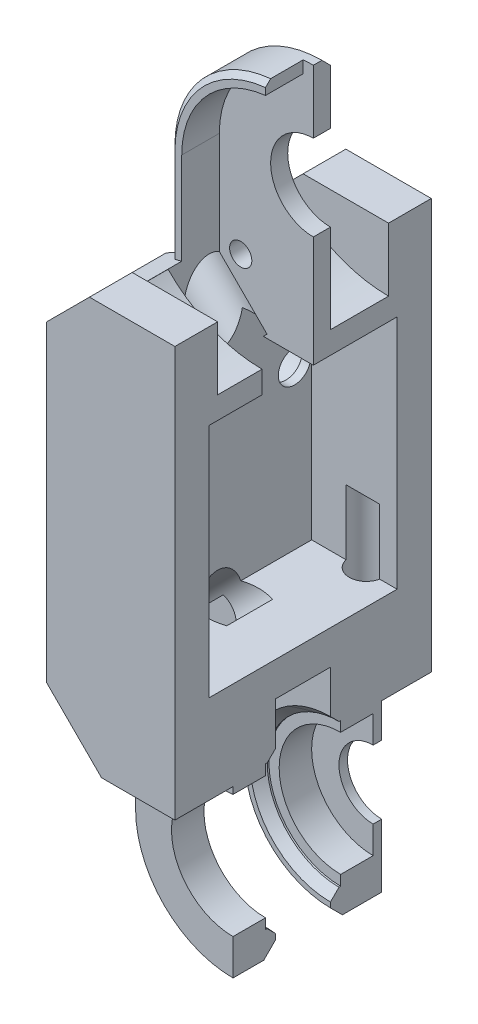
SolidWorks part; units mm, degrees
ref_plane "前视基准面" through (0, 0, 0) normal (0, 0, 1) x (1, 0, 0)
ref_plane "上视基准面" through (0, 0, 0) normal (0, 1, 0) x (1, 0, 0)
ref_plane "右视基准面" through (0, 0, 0) normal (1, 0, 0) x (0, 0, -1)
other "Configuration Table"
sketch "草图1" plane through (0, 0, 0) normal (0, 0, 1) x (1, 0, 0)
  line L0 (6.2, 9) -> (6.2, 0) construction
  line L1 (0, 0) -> (12.4, 0)
  line L2 (0, 0) -> (0, 9)
  line L4 (12.4, 0) -> (12.4, 9)
  arc A0 (0, 9) -> (12.4, 9) centre (6.2, 9) cw
  circle A1 centre (6.2, 9) radius 2.5
  circle A2 centre (1.95, 3.5) radius 0.65
  circle A3 centre (10.45, 3.5) radius 0.65
  dimension "D1" = 12.4
  dimension "D3" = 5
  dimension "D4" = 1.3
  dimension "D2" = 9
  dimension "D5" = 8.5
  dimension "D6" = 5.5
extrude "凸台-拉伸1" add sketch "草图1" along normal blind 1
sketch "草图2" plane through (0, 0, 1) normal (0, 0, 1) x (1, 0, 0)
  line L0 (0.7, 9) -> (0.7, 0)
  line L1 (0, 0) -> (12.4, 0) construction
  line L2 (11.7, 9) -> (11.7, 0)
  line L6 (0, 9) -> (0, 0)
  line L7 (0, 0) -> (12.4, 0)
  line L8 (12.4, 0) -> (12.4, 9)
  line L9 (0, 9) -> (0, 0)
  line L10 (0, 0) -> (12.4, 0)
  line L11 (12.4, 0) -> (12.4, 9)
  circle A0 centre (6.2, 9) radius 5.5
  arc A2 (12.4, 9) -> (0, 9) centre (6.2, 9) ccw
  arc A3 (12.4, 9) -> (0, 9) centre (6.2, 9) ccw
  line M5 (0, 9) -> (0, 0)
  line M6 (0, 0) -> (12.4, 0)
  line M7 (12.4, 0) -> (12.4, 9)
  arc M8 (12.4, 9) -> (0, 9) centre (6.2, 9) ccw
  dimension "D1" = 11
  dimension "D2" = 0
extrude "凸台-拉伸2" add sketch "草图2" along normal blind 2.2 contours A0 L2 L0 M6 M7 M8 M5
sketch "草图3" plane through (0, 0, 3.2) normal (0, 0, 1) x (1, 0, 0)
  line L0 (6.2, 0) -> (6.2, 14.5) construction
  line L1 (5.6, 15.6668) -> (6.8, 15.6668)
  line L2 (5.6, 15.6668) -> (5.6, 13.6792)
  line L3 (5.6, 13.6792) -> (6.8, 13.6792)
  line L4 (6.8, 15.6668) -> (6.8, 13.6792)
  line L5 (0.7, 0) -> (11.7, 0) construction
  arc A0 (11.7, 9) -> (0.7, 9) centre (6.2, 9) ccw construction
  dimension "D1" = 1.2
extrude "切除-拉伸1" cut sketch "草图3" against normal up to surface (2.2 mm away) up to face at (6.2, 5.875, 1)
sketch "草图16" plane through (0, 0, 3.2) normal (0, 0, 1) x (1, 0, 0)
  line L0 (6.2, 0) -> (6.2, 15.1709) construction
  line L2 (13.7, 0) -> (-1.3, 0)
  line L3 (13.7, 0) -> (13.7, 5)
  line L4 (13.7, 5) -> (-1.3, 5)
  line L5 (6.8, 14.4672) -> (6.8, 15.1709)
  line L6 (5.6, 15.1709) -> (5.6, 14.4672)
  line L7 (0.7, 9) -> (0.7, 0)
  line L8 (0.7, 0) -> (11.7, 0)
  line L9 (11.7, 0) -> (11.7, 9)
  line L10 (6.8, 14.4672) -> (6.8, 15.1709)
  line L11 (5.6, 15.1709) -> (5.6, 14.4672)
  line L12 (0.7, 9) -> (0.7, 0)
  line L13 (0.7, 0) -> (11.7, 0)
  line L14 (11.7, 0) -> (11.7, 9)
  line L15 (-1.3, 0) -> (-1.3, 5)
  line L16 (-1.3, 0) -> (13.7, 0)
  line L17 (-1.3, 0) -> (-1.3, -19)
  line L18 (-1.3, -19) -> (13.7, -19)
  line L19 (13.7, 0) -> (13.7, -19)
  arc A3 (11.7, 9) -> (6.8, 14.4672) centre (6.2, 9) ccw
  arc A4 (6.8, 15.1709) -> (5.6, 15.1709) centre (6.2, 9) ccw
  arc A5 (5.6, 14.4672) -> (0.7, 9) centre (6.2, 9) ccw
  arc A6 (11.7, 9) -> (6.8, 14.4672) centre (6.2, 9) ccw
  arc A7 (6.8, 15.1709) -> (5.6, 15.1709) centre (6.2, 9) ccw
  arc A8 (5.6, 14.4672) -> (0.7, 9) centre (6.2, 9) ccw
  line M18 (11.7, 0) -> (12.4, 0)
  line M19 (12.4, 0) -> (12.4, 9)
  dimension "D2" = 5
  dimension "D3" = 15
  dimension "D4" = 19
  dimension "D1" = 0
extrude "凸台-拉伸11" add sketch "草图16" along normal blind 5.9 and the other way blind 9.1 contours L19 L2 L16 L17 L18 M18 | L15 L2 L12 L4 | L3 L4 L2 M19
sketch "草图17" plane through (0, 0, -5.9) normal (0, 0, -1) x (-1, 0, 0)
  line L8 (-13.7, 5) -> (-13.7, -19)
  line L9 (-13.7, -19) -> (1.3, -19)
  line L10 (1.3, -19) -> (1.3, 5)
  line L11 (1.3, 5) -> (-0.7, 5)
  line L12 (-0.7, 5) -> (-0.7, 0)
  line L13 (-0.7, 0) -> (-12.4, 0)
  line L14 (-12.4, 0) -> (-12.4, 5)
  line L15 (-12.4, 5) -> (-13.7, 5)
  line L16 (-13.7, 5) -> (-13.7, -19)
  line L17 (-13.7, -19) -> (1.3, -19)
  line L18 (1.3, -19) -> (1.3, 5)
  line L19 (1.3, 5) -> (-0.7, 5)
  line L20 (-0.7, 5) -> (-0.7, 0)
  line L21 (-0.7, 0) -> (-12.4, 0)
  line L22 (-12.4, 0) -> (-12.4, 5)
  line L23 (-12.4, 5) -> (-13.7, 5)
  arc A1 (-11.9, 9) -> (-0.5, 9) centre (-6.2, 9) ccw
  circle A2 centre (-6.2, 9) radius 7.7
  line M14 (-0.7, 0) -> (-12.4, 0)
  line M15 (-12.4, 0) -> (-12.4, 5)
  dimension "D1" = 2
  dimension "D2" = 0
extrude "凸台-拉伸12" add sketch "草图17" against normal up to surface (5.9 mm away) contours A2 L20 M15 M14 up to face at (5.5143, 5.6, 0)
sketch "草图18" plane through (0, 0, 9.1) normal (0, 0, 1) x (1, 0, 0)
  line L8 (13.7, -19) -> (13.7, 5)
  line L9 (13.7, 5) -> (12.4, 5)
  line L10 (12.4, 5) -> (12.4, 0)
  line L11 (12.4, 0) -> (0.7, 0)
  line L12 (0.7, 0) -> (0.7, 5)
  line L13 (0.7, 5) -> (-1.3, 5)
  line L14 (-1.3, 5) -> (-1.3, -19)
  line L15 (-1.3, -19) -> (13.7, -19)
  line L16 (13.7, -19) -> (13.7, 5)
  line L17 (13.7, 5) -> (12.4, 5)
  line L18 (12.4, 5) -> (12.4, 0)
  line L19 (12.4, 0) -> (0.7, 0)
  line L20 (0.7, 0) -> (0.7, 5)
  line L21 (0.7, 5) -> (-1.3, 5)
  line L22 (-1.3, 5) -> (-1.3, -19)
  line L23 (-1.3, -19) -> (13.7, -19)
  arc A1 (0.5, 9) -> (11.9, 9) centre (6.2, 9) ccw
  circle A2 centre (6.2, 9) radius 7.7
  line M12 (12.4, 0) -> (0.7, 0)
  line M13 (0.7, 0) -> (0.7, 5)
  dimension "D1" = 2
  dimension "D2" = 0
extrude "凸台-拉伸13" add sketch "草图18" against normal blind 5.1 contours A2 L18 M13 M12
sketch "草图19" plane through (-1.3, 0, 0) normal (-1, 0, 0) x (0, 0, 1)
  line L0 (-5.9, 4.4338) -> (-5.9, 1.3) construction
  line L1 (-5.9, 5) -> (-3.4, 5)
  line L2 (-5.9, 5) -> (-5.9, 1.3)
  line L3 (-5.9, 1.3) -> (-3.4, 1.3)
  line L4 (-3.4, 5) -> (-3.4, 1.3)
  line L5 (9.1, 5) -> (6.6, 5)
  line L6 (9.1, 5) -> (9.1, 1.3)
  line L7 (9.1, 1.3) -> (6.6, 1.3)
  line L8 (6.6, 5) -> (6.6, 1.3)
  line L9 (-5.9, 4.4338) -> (-5.9, 1.3)
  line M5 (9.1, -19) -> (9.1, 5)
  line M6 (9.1, 5) -> (-5.9, 5)
  line M7 (-5.9, 5) -> (-5.9, -19)
  dimension "D1" = 2.5
  dimension "D2" = 2.5
extrude "凸台-拉伸14" add sketch "草图19" against normal up to surface (15 mm away) contours L8 L7 M6 M5 | L4 L2 L3 M6 M7 up to face at (13.7, -7, 1.6)
ref_plane "基准面2" through (0, 0, 1.6) normal (0, 0, -1) x (-1, 0, 0)
sketch "草图21" plane through (0, 0, 1.6) normal (0, 0, -1) x (-1, 0, 0)
  line L0 (1.3, -19) -> (-13.7, -19) construction
  line L1 (-11.9, -19) -> (-0.5, -19)
  line L2 (-11.9, -19) -> (-11.9, -23)
  line L4 (-0.5, -19) -> (-0.5, -23)
  line L5 (-6.2, -19) -> (-6.2, 5) construction
  line L9 (1.3, 5) -> (-13.7, 5)
  line L10 (-13.7, 5) -> (-13.7, -19)
  line L11 (-13.7, -19) -> (1.3, -19)
  line L12 (1.3, -19) -> (1.3, 5)
  line L13 (1.3, 5) -> (-13.7, 5)
  line L14 (-13.7, 5) -> (-13.7, -19)
  line L15 (-13.7, -19) -> (1.3, -19)
  line L16 (1.3, -19) -> (1.3, 5)
  arc A0 (-11.9, -23) -> (-0.5, -23) centre (-6.2, -23) ccw
  circle A1 centre (-6.2, -23) radius 3.6
  dimension "D4" = 7.2
  dimension "D2" = 11.4
  dimension "D3" = 4
  dimension "D1" = 0
extrude "凸台-拉伸15" add sketch "草图21" along normal blind 2.5 from offset 1.6 contours L2 A0 L4 L15 L1 A1
sketch "草图22" plane through (0, 0, 0) normal (0, 0, 1) x (1, 0, 0)
  circle A0 centre (6.2, -23) radius 4.2
  circle M2 centre (6.2, -23) radius 3.6
  line M4 (11.9, -19) -> (0.5, -19)
  dimension "D1" = 8.4
extrude "切除-拉伸6" cut sketch "草图22" against normal blind 0.6 and the other way blind 2.5 contours A0 M4 M2 | M2 | A0 M4
chamfer "倒角2" distance 0.5 angle 45 1 edges at (6.2, -27.2, 0)
mirror "镜向1" about plane through (0, 0, 1.6) normal (0, 0, -1) of "倒角2", "切除-拉伸6", "凸台-拉伸15"
sketch "草图23" plane through (0, 0, 1.6) normal (0, 0, -1) x (-1, 0, 0)
  line L0 (-11.9, -19) -> (-0.5, -19) construction
  circle A0 centre (-6.2, -24) radius 6.2
  circle A1 centre (-6.2, -24) radius 8.2
  point P5 (-6.2, -19)
  dimension "D1" = 2
  dimension "D3" = 12.4
  dimension "D2" = 5
extrude "切除-拉伸7" cut sketch "草图23" against normal mid plane 3.2 contours A0 | A1 A0
sketch "草图24" plane through (0, 0, -2.5) normal (0, 0, -1) x (-1, 0, 0)
  line L0 (-7.2, -21.2679) -> (-7.2, -24.7321)
  line L3 (-11.9, -19) -> (-11.9, -23)
  line L4 (-0.5, -23) -> (-0.5, -19)
  line L5 (-0.5, -19) -> (-11.9, -19)
  line L6 (-11.9, -19) -> (-11.9, -23)
  line L7 (-0.5, -23) -> (-0.5, -19)
  line L8 (-0.5, -19) -> (-11.9, -19)
  circle A0 centre (-6.2, -23) radius 3.6 construction
  arc A1 (-11.9, -23) -> (-0.5, -23) centre (-6.2, -23) ccw
  arc A2 (-11.9, -23) -> (-0.5, -23) centre (-6.2, -23) ccw
  circle A3 centre (-6.2, -23) radius 3.6
  circle A4 centre (-6.2, -23) radius 2
  point P11 (-7.2, -23)
  circle M6 centre (-6.2, -23) radius 3.6
  line M7 (-11.9, -19) -> (-11.9, -23)
  arc M8 (-11.9, -23) -> (-0.5, -23) centre (-6.2, -23) ccw
  line M9 (-0.5, -23) -> (-0.5, -19)
  line M10 (-0.5, -19) -> (-11.9, -19)
  dimension "D2" = 4
  dimension "D3" = 1
  dimension "D1" = 0
extrude "凸台-拉伸16" add sketch "草图24" along normal blind 0.5 contours M10 M7 M8 M9 M6 | A4 M6 | L0 A4
ref_plane "基准面3" through (0, 0, 1.6) normal (0, 0, -1) x (-1, 0, 0)
chamfer "倒角4" distance 2.5 angle 45 2 edges at (-1.3, 5, 1.6) (-1.3, -19, 1.6)
sketch "草图25" plane through (-1.3, 0, 0) normal (-1, 0, 0) x (0, 0, 1)
  line L0 (1.6, -14) -> (1.6, 0) construction
  line L1 (9.1, -7) -> (1.6, -7) construction
  line L2 (5.7, -18.3) -> (3.2, -18.3) construction
  line L3 (5.7, -18.3) -> (3.2, -18.3)
  line L4 (9.1, -16.5) -> (9.1, 2.5)
  line L5 (9.1, 2.5) -> (-5.9, 2.5)
  line L6 (-5.9, 2.5) -> (-5.9, -16.5)
  line L8 (9.1, -16.5) -> (9.1, 2.5)
  line L10 (-5.9, 2.5) -> (-5.9, -16.5)
  line L12 (4.45, -18.3) -> (4.45, -7) construction
  line L14 (-2.9, -4.5) -> (6.1, -4.5) construction
  line L29 (9.1, 2.5) -> (-5.9, 2.5)
  line L31 (-5.9, -16.5) -> (9.1, -16.5)
  line L32 (-5.9, -16.5) -> (9.1, -16.5)
  circle A0 centre (6.1, -4.5) radius 1.7
  circle A1 centre (-2.9, -4.5) radius 1.7
  point P17 (1.6, -16.5)
  dimension "D2" = 3.4
  dimension "D3" = 7
  dimension "D4" = 3
  dimension "D1" = 0
extrude "切除-拉伸8" cut sketch "草图25" against normal blind 2 contours A1 | A0
sketch "草图26" plane through (0.7, 0, 0) normal (-1, 0, 0) x (0, 0, 1)
  circle A0 centre (6.1, -4.5) radius 0.95
  circle A1 centre (-2.9, -4.5) radius 0.95
  dimension "D1" = 1.9
extrude "切除-拉伸9" cut sketch "草图26" against normal through all
sketch "草图27" plane through (13.7, 0, 0) normal (1, 0, 0) x (0, 0, -1)
  line L0 (5.9, 5) -> (5.9, -19) construction
  line L1 (-6.1, -6.463) -> (-4.4, -5.4815)
  line L2 (-4.4, -5.4815) -> (-4.4, -3.5185)
  line L3 (-4.4, -3.5185) -> (-6.1, -2.537)
  line L4 (-6.1, -2.537) -> (-7.8, -3.5185)
  line L5 (-7.8, -3.5185) -> (-7.8, -5.4815)
  line L6 (-7.8, -5.4815) -> (-6.1, -6.463)
  line L7 (2.9, -6.463) -> (4.6, -5.4815)
  line L8 (4.6, -5.4815) -> (4.6, -3.5185)
  line L9 (4.6, -3.5185) -> (2.9, -2.537)
  line L10 (2.9, -2.537) -> (1.2, -3.5185)
  line L11 (1.2, -3.5185) -> (1.2, -5.4815)
  line L12 (1.2, -5.4815) -> (2.9, -6.463)
  circle A0 centre (-6.1, -4.5) radius 1.7 construction
  circle A1 centre (2.9, -4.5) radius 1.7 construction
  dimension "D1" = 3.4
extrude "切除-拉伸10" cut sketch "草图27" against normal blind 2
ref_plane "基准面4" through (0, 0, 1.6) normal (0, 0, 1) x (1, 0, 0)
sketch "草图30" plane through (0, 0, 9.1) normal (0, 0, 1) x (1, 0, 0)
  line L0 (-1.3, -7) -> (13.7, -7) construction
  line L1 (13.7, -31.8239) -> (6.2, -31.8239)
  line L2 (13.7, -31.8239) -> (13.7, 17.8239)
  line L3 (13.7, 17.8239) -> (6.2, 17.8239)
  line L4 (6.2, -31.8239) -> (6.2, 17.8239)
  line L6 (13.7, 5) -> (1.2, 5)
  line L8 (-1.3, 2.5) -> (-1.3, -16.5)
  line L10 (1.2, -19) -> (13.7, -19)
  line L11 (13.7, -19) -> (13.7, 5)
  line L12 (13.7, 5) -> (1.2, 5)
  line L14 (-1.3, 2.5) -> (-1.3, -16.5)
  line L16 (1.2, -19) -> (13.7, -19)
  line L17 (13.7, -19) -> (13.7, 5)
  line L18 (13.7, -31.8239) -> (-7.3517, -31.8239)
  line L19 (13.7, -31.8239) -> (13.7, 17.8239)
  line L20 (13.7, 17.8239) -> (-7.3517, 17.8239)
  line L21 (-7.3517, -31.8239) -> (-7.3517, 17.8239)
  line L25 (1.2, 5) -> (-1.3, 2.5)
  line L31 (1.2, 5) -> (-1.3, 2.5)
  line L33 (-1.3, -16.5) -> (1.2, -19)
  line L34 (-1.3, -16.5) -> (1.2, -19)
  point P12 (6.2, -7)
  line M11 (13.7, 5) -> (1.2, 5)
  line M15 (1.2, -19) -> (13.7, -19)
  line M16 (13.7, -19) -> (13.7, 5)
  dimension "D1" = 0
extrude "切除-拉伸11" cut sketch "草图30" against normal through all contours L4 L2 L3 M11 | L4 L0 L19 M11 | L0 L4 M15 M16 | L4 L1 L2 M15
sketch "草图31" plane through (6.2, 0, 0) normal (1, 0, 0) x (0, 0, -1)
  line L0 (-3.2, -15.8) -> (0, -15.8) construction
  line L1 (-7.1, 0) -> (3.9, 0)
  line L2 (-7.1, 0) -> (-7.1, -13.8)
  line L3 (-7.1, -13.8) -> (3.9, -13.8)
  line L4 (3.9, 0) -> (3.9, -13.8)
  line L5 (-4, 0) -> (-1, 0) construction
  line L6 (-3.2, -15.8) -> (0, -15.8)
  line L7 (5.9, -19) -> (5.9, 5) construction
  point P8 (-1.6, -15.8)
  point P9 (-1.6, -13.8)
  line M27 (-1, 0) -> (-4, 0)
  circle M32 centre (-6.1, -4.5) radius 0.95
  circle M33 centre (2.9, -4.5) radius 0.95
  dimension "D1" = 2
  dimension "D2" = 2
extrude "切除-拉伸12" cut sketch "草图31" against normal blind 5 contours L4 L1 L2 L3 M27 M32 M33
sketch "草图32" plane through (-8.9, -8.9, 0) normal (-0.7071, -0.7071, 0) x (0, 0, 1)
  line L0 (1.6, 8.25) -> (1.6, -8.25) construction
  line L2 (-5.9, -10.748) -> (9.1, -10.748) construction
  circle A0 centre (1.6, -11.248) radius 1.5
  dimension "D1" = 3
  dimension "D2" = 0.5
extrude "切除-拉伸13" cut sketch "草图32" against normal blind 5
sketch "草图33" plane through (-1.9, 1.9, 0) normal (-0.7071, 0.7071, 0) x (0, 0, 1)
  line L0 (1.6, 4.125) -> (1.6, -4.125) construction
  line L1 (9.1, 0.8485) -> (-5.9, 0.8485) construction
  circle A0 centre (1.6, 1.2485) radius 1.5
  dimension "D2" = 3
  dimension "D1" = 0.4
extrude "切除-拉伸14" cut sketch "草图33" against normal blind 5
sketch "草图35" plane through (0, -19, 0) normal (0, -1, 0) x (1, 0, 0)
  line L0 (1.2, 9.1) -> (6.2, 9.1) construction
  line L2 (6.2, 5.7) -> (6.2, 9.1) construction
  line L3 (6.2, -5.9) -> (6.2, -3) construction
  line L4 (1.2, -5.9) -> (6.2, -5.9) construction
  circle A0 centre (4.2, 7.1) radius 1
  circle A1 centre (4.2, -4.1) radius 1
  dimension "D1" = 2
  dimension "D5" = 1.8
  dimension "D2" = 2
  dimension "D3" = 2
  dimension "D4" = 2
extrude "切除-拉伸15" cut sketch "草图35" against normal blind 8
chamfer "倒角5" distance 1 angle 45 2 edges at (4.2, -11, 7.1) (4.2, -11, -3.9)
sketch "草图36" plane through (0, 0, 9.1) normal (0, 0, 1) x (1, 0, 0)
  line L0 (1.9071, -19) -> (-1.3, -15.7929)
  line L1 (1.2, -19) -> (6.2, -19) construction
  line L2 (-1.3, 2.5) -> (-1.3, -16.5) construction
  line L3 (-1.3, -16.5) -> (1.2, -19) construction
  line L4 (1.2, -19) -> (-1.5121, -19)
  line L5 (-1.5121, -19) -> (-1.3, -16.5)
  line L10 (1.2, -19) -> (6.2, -19)
  line L11 (6.2, -19) -> (6.2, 5)
  line L12 (6.2, 5) -> (1.2, 5)
  line L13 (1.2, 5) -> (-1.3, 2.5)
  line L14 (-1.3, 2.5) -> (-1.3, -16.5)
  line L15 (-1.3, -16.5) -> (1.2, -19)
  line L16 (1.2, -19) -> (6.2, -19)
  line L17 (6.2, -19) -> (6.2, 5)
  line L18 (6.2, 5) -> (1.2, 5)
  line L19 (1.2, 5) -> (-1.3, 2.5)
  line L20 (-1.3, 2.5) -> (-1.3, -16.5)
  line M8 (1.2, -19) -> (6.2, -19)
  line M12 (-1.3, 2.5) -> (-1.3, -16.5)
  line M13 (-1.3, -16.5) -> (1.2, -19)
  dimension "D1" = 0.5
  dimension "D2" = 0
extrude "切除-拉伸16" cut sketch "草图36" against normal blind 3.4 contours L0 M8 M12 M13
sketch "草图37" plane through (-8.9, -8.9, 0) normal (-0.7071, -0.7071, 0) x (0, 0, 1)
  line L0 (3.2, -13.2936) -> (3.2, -10.748)
  line L1 (0, -13.1546) -> (0, -10.748)
  line L9 (0.1858, -10.748) -> (-5.9, -10.748)
  line L10 (-5.9, -10.748) -> (-5.9, -14.2836)
  line L11 (-3, -13.2936) -> (0, -13.2936)
  line L12 (0, -13.2936) -> (0, -13.1546)
  line L13 (0, -13.1546) -> (3.2, -13.1546)
  line L14 (3.2, -13.1546) -> (3.2, -13.2936)
  line L15 (3.2, -13.2936) -> (5.7, -13.2936)
  line L16 (5.7, -13.2936) -> (5.7, -10.748)
  line L17 (5.7, -10.748) -> (3.0142, -10.748)
  line L18 (0.1858, -10.748) -> (-5.9, -10.748)
  line L20 (-3, -13.2936) -> (0, -13.2936)
  line L21 (0, -13.2936) -> (0, -13.1546)
  line L22 (0, -13.1546) -> (3.2, -13.1546)
  line L23 (3.2, -13.1546) -> (3.2, -13.2936)
  line L24 (3.2, -13.2936) -> (5.7, -13.2936)
  line L25 (5.7, -13.2936) -> (5.7, -10.748)
  line L26 (5.7, -10.748) -> (3.0142, -10.748)
  line L31 (-5.9, -10.748) -> (-5.9, -14.2836)
  line L32 (-5.9, -14.2836) -> (-3, -14.2836)
  line L33 (-5.9, -14.2836) -> (-3, -14.2836)
  line L34 (-3, -14.2836) -> (-3, -13.2936)
  line L35 (-3, -14.2836) -> (-3, -13.2936)
  arc A1 (0.1858, -10.748) -> (3.0142, -10.748) centre (1.6, -11.248) ccw
  arc A2 (0.1858, -10.748) -> (3.0142, -10.748) centre (1.6, -11.248) ccw
  line M11 (0.1858, -10.748) -> (-5.9, -10.748)
  line M15 (0, -13.1546) -> (3.2, -13.1546)
  line M19 (5.7, -10.748) -> (3.0142, -10.748)
  arc M20 (3.0142, -10.748) -> (0.1858, -10.748) centre (1.6, -11.248) cw
  dimension "D1" = 0
extrude "切除-拉伸17" cut sketch "草图37" against normal up to surface (0.5 mm away) contours L1 L0 M15 M19 M20 M11 up to face at (0.3036, -17.3964, 7.4)
sketch "草图38" plane through (0, 0, -5.9) normal (0, 0, -1) x (-1, 0, 0)
  line L0 (-1.9071, -19) -> (1.3, -15.7929)
  line L1 (-1.2, -19) -> (-6.2, -19) construction
  line L2 (1.3, 2.5) -> (1.3, -16.5) construction
  line L3 (-1.2, -19) -> (1.3, -16.5) construction
  line L4 (-1.9071, -19) -> (2.3988, -20.3676)
  line L5 (2.3988, -20.3676) -> (1.3, -15.7929)
  dimension "D1" = 0.5
extrude "切除-拉伸18" cut sketch "草图38" against normal up to surface (2.9 mm away) up to face at (3.4028, -22.1686, -3)
sketch "草图39" plane through (-8.9, -8.9, 0) normal (-0.7071, -0.7071, 0) x (0, 0, 1)
  line L0 (3.2, -13.1546) -> (3.2, -13.0554)
  line L1 (3.2, -13.0554) -> (0, -13.0554)
  line L2 (0, -13.0554) -> (0, -13.1546)
  line L5 (0, -13.1546) -> (3.2, -13.1546)
  line L6 (3.2, -13.1546) -> (3.2, -10.748)
  line L7 (3.2, -10.748) -> (3.0142, -10.748)
  line L8 (0.1858, -10.748) -> (0, -10.748)
  line L9 (0, -10.748) -> (0, -13.1546)
  line L11 (3.2, -13.1546) -> (3.2, -10.748)
  line L12 (3.2, -10.748) -> (3.0142, -10.748)
  line L13 (0.1858, -10.748) -> (0, -10.748)
  line L14 (0, -10.748) -> (0, -13.1546)
  line L18 (0, -13.1546) -> (3.2, -13.1546)
  arc A1 (0.1858, -10.748) -> (3.0142, -10.748) centre (1.6, -11.248) ccw
  arc A2 (0.1858, -10.748) -> (3.0142, -10.748) centre (1.6, -11.248) ccw
  line M7 (3.2, -10.748) -> (3.2, -13.1546)
  line M8 (3.2, -13.1546) -> (3.2, -13.2936)
  dimension "D1" = 0
extrude "切除-拉伸19" cut sketch "草图39" against normal blind 2 contours A2 L13 L14 L18 L12 M7 | L18 L2 L1 L0 M8
chamfer "倒角6" distance 0.7 angle 45 4 edges at (2.1695, -27.0305, 0) (0.5, -20.65, 0) (2.1695, -27.0305, 3.2) (0.5, -20.65, 3.2)
chamfer "倒角7" distance 0.5 angle 45 6 edges at (4.9194, -19, -0.25) (4.9194, -19, 3.45) (5.5519, -18.8503, 0) (4.3258, -19, 0) (4.3258, -19, 3.2) (5.5519, -18.8503, 3.2)
chamfer "倒角8" distance 0.5 angle 45 2 edges at (0, 6.4, 0) (1.8159, 13.3841, 0)
chamfer "倒角9" distance 0.3 angle 45 2 edges at (0, 6.4, 3.2) (1.6087, 13.1665, 3.2)
chamfer "倒角10" distance 1.7 angle 30 2 edges at (0.7, 4.5, 4.9) (0.7, 4.5, -1.7)
sketch "草图40" plane through (-8.9, -8.9, 0) normal (-0.7071, -0.7071, 0) x (0, 0, 1)
  line L0 (3.2, -13.1546) -> (3.2, -10.748) construction
  line L1 (3.2, -12.487) -> (0, -12.487)
  line L2 (3.2, -12.487) -> (3.2, -14.01)
  line L3 (3.2, -14.01) -> (0, -14.01)
  line L4 (0, -12.487) -> (0, -14.01)
  line L5 (0, -13.1546) -> (0, -14.2836) construction
extrude "切除-拉伸20" cut sketch "草图40" against normal up to surface (2 mm away) up to face at (0.9172, -15.8887, 1.6)
